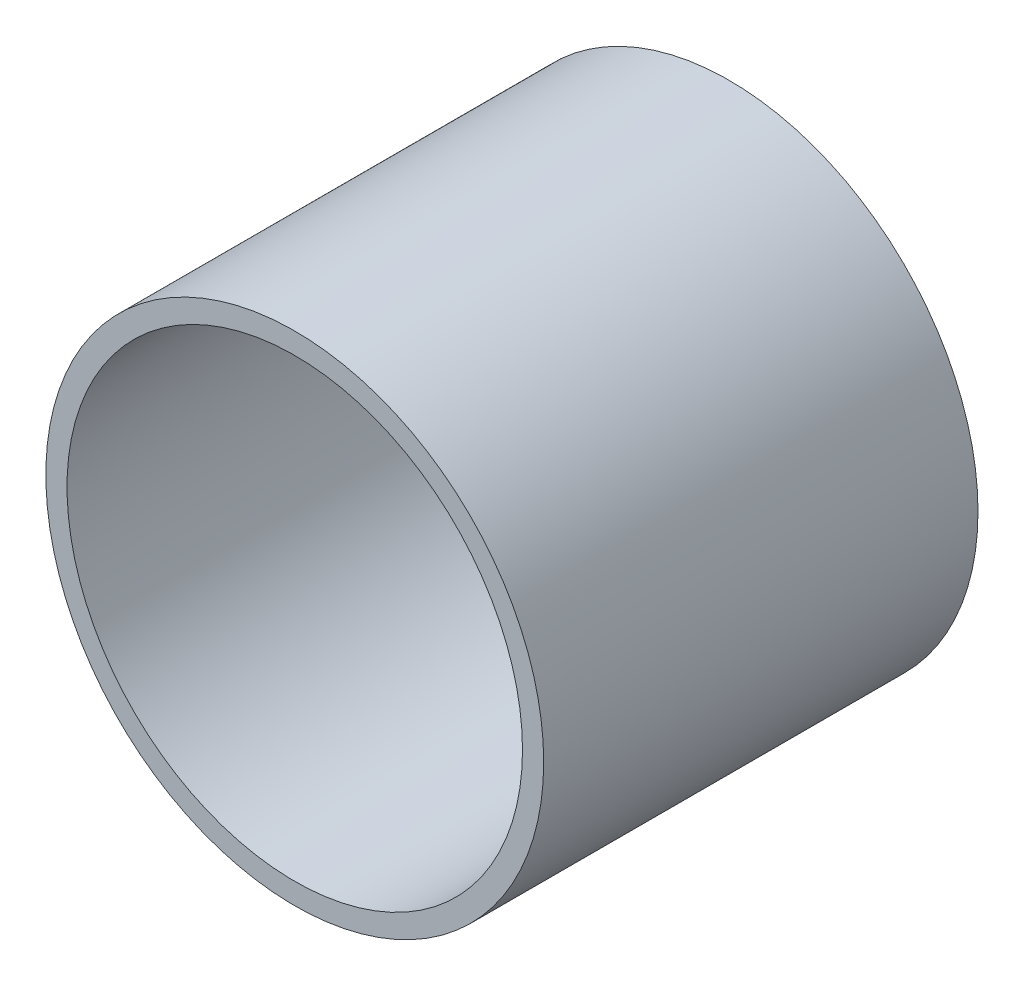
SolidWorks part; units mm, degrees
ref_plane "Front Plane" through (0, 0, 0) normal (0, 0, 1) x (1, 0, 0)
ref_plane "Top Plane" through (0, 0, 0) normal (0, 1, 0) x (1, 0, 0)
ref_plane "Right Plane" through (0, 0, 0) normal (1, 0, 0) x (0, 0, -1)
sketch "Sketch1" plane through (0, 0, 0) normal (0, 0, 1) x (1, 0, 0)
  circle A0 centre (0, 0) radius 59.69
  circle A2 centre (0, 0) radius 54.61
  dimension "D1" = 119.38
  dimension "D2" = 5.08
extrude "Boss-Extrude1" add sketch "Sketch1" along normal blind 104.14 contours A0 A2 region at (-58.0017, 0, 0)
sketch "Sketch2" plane through (0, 0, 0) normal (0, 0, -1) x (-1, 0, 0)
  line L0 (-48.26, 6.35) -> (-54.2396, 6.35)
  line L1 (-48.26, -6.35) -> (-54.2396, -6.35)
  circle A1 centre (-48.26, 0) radius 3.3782
  arc A4 (-48.26, -6.35) -> (-48.26, 6.35) centre (-48.26, 0) ccw
  circle A5 centre (0, 0) radius 54.61 construction
  circle A8 centre (0, 0) radius 54.61
  arc A9 (-54.2396, 6.35) -> (-54.2396, -6.35) centre (0, 0) ccw
  dimension "D1" = 0
  dimension "D2" = 48.26
extrude "Boss-Extrude2" add sketch "Sketch2" against normal blind 6.35
pattern_circular "CirPattern1" count 4 over 360 about axis through (0, 0, 104.14) along (0, 0, -1) of "Boss-Extrude2" reverse direction yes
